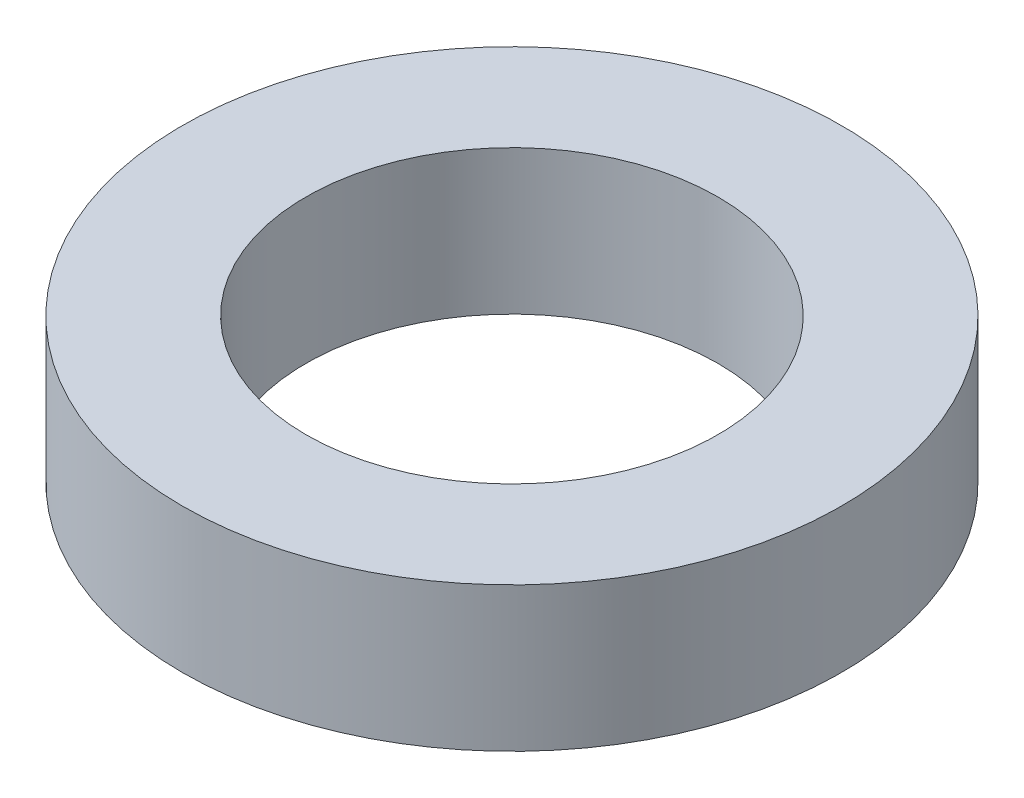
SolidWorks part; units mm, degrees
ref_plane "Front Plane" through (0, 0, 0) normal (0, 0, 1) x (1, 0, 0)
ref_plane "Top Plane" through (0, 0, 0) normal (0, 1, 0) x (1, 0, 0)
ref_plane "Right Plane" through (0, 0, 0) normal (1, 0, 0) x (0, 0, -1)
sketch "Sketch1" plane through (0, 0, 0) normal (0, 1, 0) x (1, 0, 0)
  circle A0 centre (0, 0) radius 16
  circle A1 centre (0, 0) radius 10
  dimension "D1" = 20
  dimension "D2" = 32
extrude "Boss-Extrude1" add sketch "Sketch1" along normal mid plane 7
equation "\"Ns\" = 80"
equation "\"Np_b\" = 55"
equation "\"Np_s\" = 35"
equation "\"Nr_b\" = 190"
equation "\"num_planet\" = 5"
equation "\"module\" = 0.5"
equation "\"fw_p_b\" = 21.365107882670422"
equation "\"fw_r_b\" = 21.365107882670422"
equation "\"fw_s_calc\" = 4.872946430626146"
equation "\"fw_r_s\" = 14.31085678360617"
equation "\"fw_p_s\" = 15.81085678360617"
equation "\"fw_s_used\" = 44.67596466627659"
equation "\"pressure_angle\" = 20.0"
equation "\"motor_OD\" = 106.8"
equation "\"motor_height\" = 47.6"
equation "\"motor_mount_hole_PCD\" = 40"
equation "\"motor_mount_hole_dia\" = 5"
equation "\"motor_mount_hole_num\" = 4"
equation "\"wire_slot_dist_from_center\" = 45.5"
equation "\"wire_slot_length\" = 10"
equation "\"wire_slot_radius\" = 3"
equation "\"motor_output_hole_PCD\" = 23"
equation "\"motor_output_hole_dia\" = 4"
equation "\"motor_output_hole_num\" = 4"
equation "\"h_a\" = 0.5"
equation "\"h_f\" = 0.625"
equation "\"clr_tip_root\" = 0.125"
equation "\"dp_r_b\" = 95.0"
equation "\"db_r_b\" = 89.2707989746613"
equation "\"alpha_r_b\" = 0.8539582918412414"
equation "\"beta_r_b\" = 2.655285004735114"
equation "\"bearing_ID\" = 75"
equation "\"bearing_OD\" = 95"
equation "\"bearing_height\" = 10"
equation "\"clearance_planet\" = 1.5"
equation "\"case_dist\" = 6.5"
equation "\"Motor_case_OD_max\" = 131.3"
equation "\"case_mounting_PCD\" = 123.8"
equation "\"bearing mount thickness\" = 8"
equation "\"case_mounting_hole_dia\" = 3"
equation "\"output_mounting_PCD\" = 103"
equation "\"output_mounting_hole_dia\" = 4"
equation "\"clearance_case_mount_holes_shell_thickness\" = 1"
equation "\"motor_case_OD_base\" = 121.8"
equation "\"sec_carrier_thickness\" = 5"
equation "\"sun_coupler_hub_thickness\" = 4"
equation "\"clearance_sun_coupler_sec_carrier\" = 1.5"
equation "\"clearance_motor_and_case\" = 5"
equation "\"Motor_case_thickness\" = 2.5"
equation "\"Motor_case_ID\" = 116.8"
equation "\"case_mounting_hole_shift\" = 1.0"
equation "\"output_mounting_nut_wrench_size\" = 7"
equation "\"output_mounting_nut_thickness\" = 3.2"
equation "\"case_mounting_hole_allen_socket_dia\" = 5.5"
equation "\"output_mounting_nut_depth\" = 3"
equation "\"case_mounting_bolt_depth\" = 4.5"
equation "\"ring_radial_thickness\" = 5"
equation "\"ring_OD_b\" = 105.0"
equation "\"ring_to_chamfer_clearance\" = 1.5"
equation "\"Motor_case_OD_base_to_chamfer\" = 5"
equation "\"pattern_offset_from_motor_case_OD_base\" = 3"
equation "\"pattern_bulge_dia\" = 3"
equation "\"pattern_num_bulge\" = 18"
equation "\"pattern_depth\" = 2"
equation "\"case_mounting_wrench_size\" = 5.5"
equation "\"case_mounting_nut_clearance\" = 2"
equation "\"base_plate_thickness\" = 4"
equation "\"case_mounting_nut_thickness\" = 2.4"
equation "\"case_mounting_surface_height\" = 4"
equation "\"central_hole_offset_from_motor_mount_PCD\" = 5"
equation "\"driver_upper_holes_dist_from_center\" = 29"
equation "\"driver_lower_holes_dist_from_center\" = 13"
equation "\"driver_side_holes_dist_from_center\" = 22.5"
equation "\"driver_mount_holes_dia\" = 3"
equation "\"driver_mount_inserts_OD\" = 4.8"
equation "\"driver_mount_thickness\" = 1.5"
equation "\"driver_mount_height\" = 6"
equation "\"air_flow_hole_offset\" = 3"
equation "\"pressure angle\" = 20.0"
equation "\"h_b\" = 0.625"
equation "\"planet_pin_bolt_dia\" = 5"
equation "\"planet_pin_socket_head_dia\" = 8.5"
equation "\"carrier_PCD\" = 67.5"
equation "\"planet_shaft_dia\" = 8"
equation "\"planet_shaft_step_offset\" = 1"
equation "\"carrier_trapezoidal_support_sun_offset\" = 5"
equation "\"carrier_trapezoidal_support_hole_PCD_offset_bearing_ID\" = 4"
equation "\"carrier_trapezoidal_support_hole_dia\" = 3"
equation "\"carrier_trapezoidal_support_hole_socket_head_dia\" = 5.5"
equation "\"carrier_bearing_step_width\" = 1.5"
equation "\"standard_clearance_1_5mm\" = 1.5"
equation "\"standard_fillet_1_5mm\" = 1.5"
equation "\"sun_shaft_bearing_ID\" = 8"
equation "\"sun_shaft_bearing_OD\" = 16"
equation "\"sun_shaft_bearing_width\" = 5"
equation "\"standard_bearing_insertion_chamfer\" = 0.5"
equation "\"carrier_trapezoidal_support_hole_wrench_size\" = 5.5"
equation "\"planet_pin_bolt_wrench_size\" = 8"
equation "\"planet_bearing_OD\" = 12"
equation "\"planet_bearing_width\" = 3.5"
equation "\"planet_bore\" = 10"
equation "\"dp_s\" = 40.0"
equation "\"db_s\" = 37.58770483143634"
equation "\"alpha_s\" = 0.8539582918412272"
equation "\"beta_s\" = 0.5420834163175456"
equation "\"dp_p_b\" = 27.5"
equation "\"db_p_b\" = 25.84154707161248"
equation "\"alpha_p_b\" = 0.8539582918412449"
equation "\"beta_p_b\" = 1.564810689044783"
equation "\"sun_hub_dia\" = 30.0"
equation "\"sun_central_bolt_dia\" = 5"
equation "\"sun_central_bolt_socket_head_dia\" = 8.5"
equation "\"motor_output_hole_CSK_OD\" = 8"
equation "\"motor_output_hole_CSK_head_height\" = 2.0"
equation "\"bearing_retainer_thickness\" = 2"
equation "\"dp_p_s\" = 17.5"
equation "\"db_p_s\" = 16.444620863753396"
equation "\"alpha_p_s\" = 0.8539582918412556"
equation "\"beta_p_s\" = 3.434940559174632"
equation "\"Nr_s\" = 170"
equation "\"clr_tip_root_s\" = 0.125"
equation "\"dp_r_s\" = 85.0"
equation "\"db_r_s\" = 79.87387276680222"
equation "\"alpha_r_s\" = 0.8539582918412307"
equation "\"beta_r_s\" = 2.766740113094226"
equation "\"small_ring_case_thickness\" = 4"
equation "\"carrier_thickness\" = 4"
equation "\"small_ring_output_wall_thickness\" = 5"
equation "\"small_ring_output_wall_to_bearing_shaft_attachement_hole_dia\" = 4"
equation "\"small_ring_output_wall_to_bearing_shaft_attachement_hole_depth\" = 6.5"
equation "\"small_ring_output_wall_to_bearing_shaft_attachement_nut_wrench\" = 7"
equation "\"small_ring_output_wall_to_bearing_shaft_attachement_nut_thickness\" = 3.2"
equation "\"small_ring_output_wall_to_bearing_shaft_attachement_hole_pcd\" = 12"
equation "\"small_ring_output_wall_to_bearing_shaft_attachement_hole_num\" = 3"
equation "\"small_ring_output_wall_to_bearing_shaft_attachement_hole_CSK_OD\" = 8"
equation "\"small_ring_output_wall_to_bearing_shaft_attachement_hole_CSK_head_height\" = 2.0"
equation "\"carrier_small_ring_inner_bearing_ID\" = 20"
equation "\"carrier_small_ring_inner_bearing_OD\" = 32"
equation "\"carrier_small_ring_inner_bearing_height\" = 7"
equation "\"carrier_small_ring_inner_bearing_flap\" = 2"
equation "\"D1@Boss-Extrude1\"=\"carrier_small_ring_inner_bearing_height\""
equation "\"D1@Sketch1\"=\"carrier_small_ring_inner_bearing_ID\""
equation "\"D2@Sketch1\"=\"carrier_small_ring_inner_bearing_OD\""
